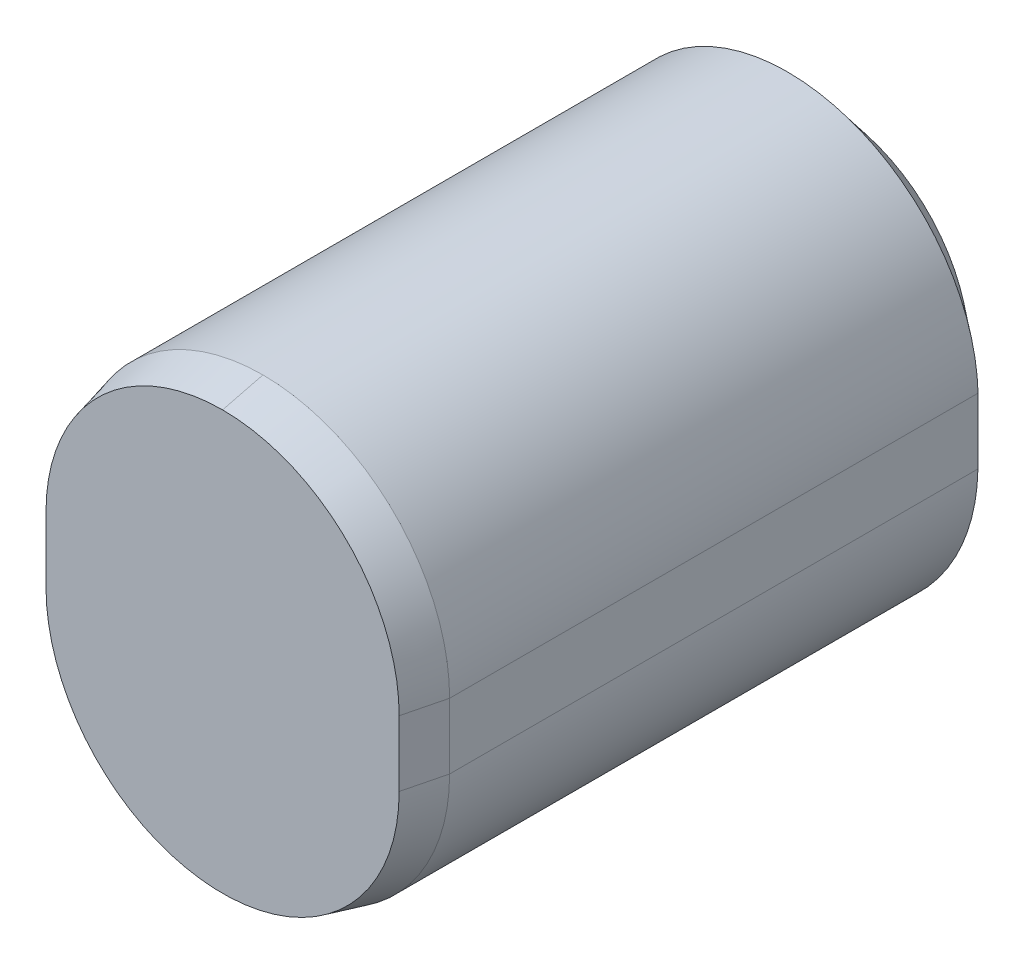
SolidWorks part; units mm, degrees
ref_plane "Front Plane" through (0, 0, 0) normal (0, 0, 1) x (1, 0, 0)
ref_plane "Top Plane" through (0, 0, 0) normal (0, 1, 0) x (1, 0, 0)
ref_plane "Right Plane" through (0, 0, 0) normal (1, 0, 0) x (0, 0, -1)
sketch "Sketch1" plane through (0, 0, 0) normal (0, 0, 1) x (1, 0, 0)
  line L2 (-58.7375, -10.3187) -> (-58.7375, 10.3188)
  line L4 (58.7375, -10.3188) -> (58.7375, 10.3187)
  line L5 (-58.7375, -10.3187) -> (58.7375, 10.3187) construction
  line L6 (-58.7375, 10.3188) -> (58.7375, -10.3188) construction
  arc A0 (-58.7375, 10.3188) -> (58.7375, 10.3187) centre (0, 10.3187) cw
  arc A1 (58.7375, -10.3188) -> (-58.7375, -10.3187) centre (0, -10.3188) cw
  point P0 (0, 0)
  point P9 (0, 69.0562)
  point P10 (0, -69.0563)
  dimension "D1" = 117.475
  dimension "D2" = 138.1125
extrude "Boss-Extrude1" add sketch "Sketch1" along normal blind 190.5
sketch "Sketch2" plane through (0, 0, 0) normal (0, 0, -1) x (-1, 0, 0)
  line L2 (-44.45, -8.89) -> (-44.45, 8.89)
  line L4 (44.45, -8.89) -> (44.45, 8.89)
  line L5 (-44.45, -8.89) -> (44.45, 8.89) construction
  line L6 (-44.45, 8.89) -> (44.45, -8.89) construction
  arc A0 (-44.45, 8.89) -> (44.45, 8.89) centre (0, 8.89) cw
  arc A2 (-44.45, -8.89) -> (44.45, -8.89) centre (0, -8.89) ccw
  point P0 (0, 0)
  point P8 (0, 53.34)
  point P9 (0, -53.34)
  dimension "D1" = 106.68
  dimension "D2" = 88.9
sketch "Sketch3" plane through (0, 0, 0) normal (1, 0, 0) x (0, 0, -1)
  line L0 (0, 53.34) -> (-12.7, 69.0563) construction
  line L1 (0, 8.89) -> (0, 53.34) construction
  line L2 (0, 69.0563) -> (-190.5, 69.0563) construction
  line L3 (0, 10.3188) -> (0, 69.0563) construction
  line L6 (-25.1271, 84.4348) -> (11.6486, 38.9248)
  line L7 (-25.1271, 84.4348) -> (23.1035, 84.4348)
  line L8 (23.1035, 84.4348) -> (11.6486, 38.9248)
  dimension "D1" = 12.7
sweep "Cut-Sweep1" cut profiles "Sketch3" path "Sketch2"
sketch "Sketch4" plane through (0, 0, 190.5) normal (0, 0, 1) x (1, 0, 0)
  line L2 (-55.5625, -10.3188) -> (-55.5625, 10.3187)
  line L4 (55.5625, -10.3188) -> (55.5625, 10.3188)
  line L5 (-55.5625, -10.3188) -> (55.5625, 10.3188) construction
  line L6 (-55.5625, 10.3187) -> (55.5625, -10.3188) construction
  arc A0 (-55.5625, 10.3187) -> (55.5625, 10.3188) centre (0, 10.3188) cw
  arc A1 (-55.5625, -10.3188) -> (55.5625, -10.3188) centre (0, -10.3188) ccw
  point P0 (0, 0)
  point P8 (0, 65.8813)
  point P9 (0, -65.8812)
  dimension "D1" = 131.7625
  dimension "D2" = 111.125
sketch "Sketch5" plane through (0, 0, 0) normal (1, 0, 0) x (0, 0, -1)
  line L0 (-190.5, 65.8813) -> (-177.8, 69.0563)
  line L1 (-190.5, 65.8813) -> (-190.5, 10.3188) construction
  line L2 (-12.7, 69.0563) -> (-190.5, 69.0563) construction
  line L3 (-190.5, 65.8813) -> (-190.5, 69.0563)
  line L4 (-190.5, 69.0563) -> (-177.8, 69.0563)
  dimension "D1" = 12.7
sweep "Cut-Sweep2" cut profiles "Sketch5" path "Sketch4"
equation "\"D1@Sketch2\"=4+1/5"
equation "\"D1@Sketch4\"=5+3/16"
equation "\"D2@Sketch4\"=4+3/8"
